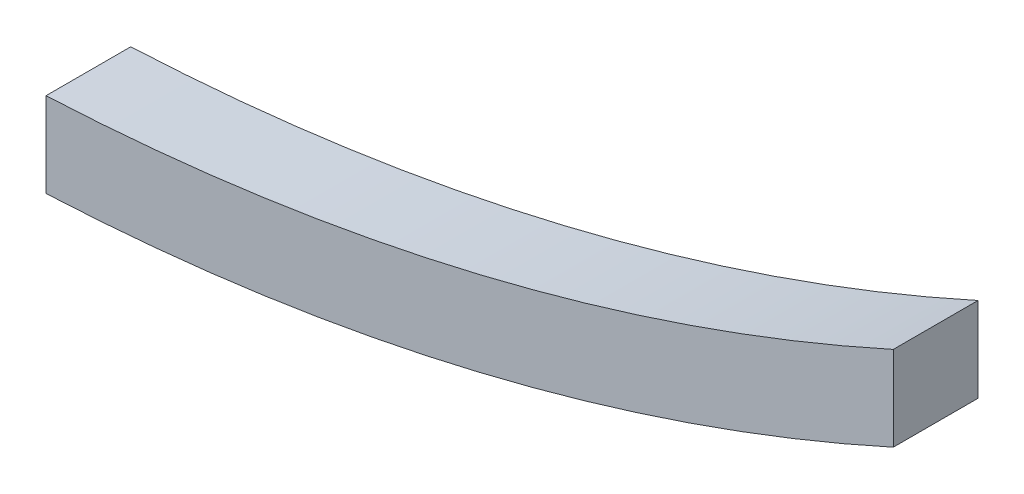
SolidWorks part; units mm, degrees
ref_plane "Ebene vorne" through (0, 0, 0) normal (0, 0, 1) x (1, 0, 0)
ref_plane "Ebene oben" through (0, 0, 0) normal (0, 1, 0) x (1, 0, 0)
ref_plane "Ebene rechts" through (0, 0, 0) normal (1, 0, 0) x (0, 0, -1)
sketch "Skizze1" plane through (0, 0, 0) normal (0, 0, 1) x (1, 0, 0)
  line L0 (0, 0) -> (0, 30)
  line L1 (300, 72.2031) -> (300, 102.2031)
  arc A0 (0, 0) -> (300, 72.2031) centre (-38.6735, 820.0302) ccw
  arc A1 (0, 30) -> (300, 102.2031) centre (-38.6735, 850.0302) ccw
  dimension "D1" = 30
  dimension "D2" = 30
  dimension "D3" = 300
extrude "Aufsatz-Linear austragen1" add sketch "Skizze1" along normal blind 30
